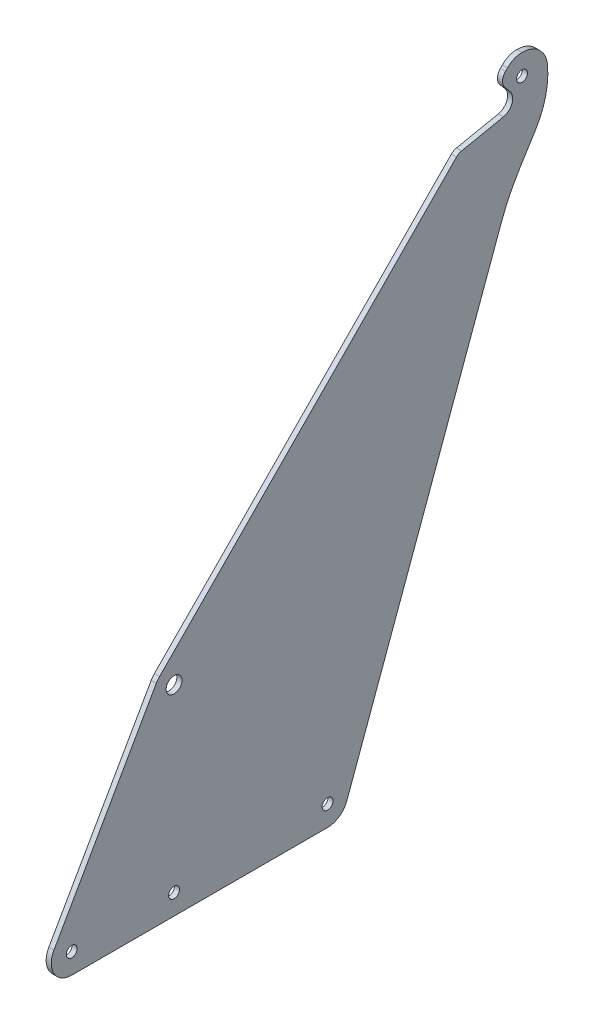
SolidWorks part; units mm, degrees
material "1060 Alloy"
ref_plane "Front Plane" through (0, 0, 0) normal (0, 0, 1) x (1, 0, 0)
ref_plane "Top Plane" through (0, 0, 0) normal (0, 1, 0) x (1, 0, 0)
ref_plane "Right Plane" through (0, 0, 0) normal (1, 0, 0) x (0, 0, -1)
sketch "Sketch5" plane through (0, 0, 0) normal (-1, 0, 0) x (0, 0, 1)
  line L0 (0, 0) -> (473.0768, -42.2261)
  line L1 (0, 0) -> (122.9281, 458.7738)
  line L2 (0, 0) -> (75.945, 21.568)
  line L4 (0, 0) -> (-8.1905, 78.5222)
  line L6 (-8.1905, 78.5222) -> (19.0819, 71.2146)
  line L7 (75.945, 21.568) -> (73.4348, -6.5547)
  line L8 (75.945, 21.568) -> (-215.9, 219.1278)
  line L9 (-215.9, 219.1278) -> (-8.1905, 78.5222)
  line L10 (0, 0) -> (745.3451, 0) construction
  point P2 (0, 0)
  dimension "D1" = 250.825
  dimension "D2" = 352.425
  dimension "D3" = 75
  dimension "D4" = 5.101
  dimension "D5" = 215.9
sketch "Sketch1" plane through (0, 0, 0) normal (1, 0, 0) x (0, 0, -1)
  line L0 (-74.539, -105.3537) -> (-11.039, 6.2793)
  line L2 (-63.5, -124.333) -> (95.25, -124.333)
  line L5 (107.181, -115.985) -> (227.831, 214.7758)
  line L6 (206.8534, 228.0412) -> (-9.0466, 8.9134)
  arc A0 (-9.0466, 8.9134) -> (-11.039, 6.2793) centre (0, 0) ccw
  arc A1 (95.25, -124.333) -> (107.181, -115.985) centre (95.25, -111.633) ccw
  arc A2 (-74.539, -105.3537) -> (-63.5, -124.333) centre (-63.5, -111.633) ccw
  arc A3 (227.831, 214.7758) -> (206.8534, 228.0412) centre (215.9, 219.1278) ccw
  dimension "D1" = 158.75
  dimension "D2" = 111.633
  dimension "D4" = 25.4
  dimension "D5" = 95.25
  dimension "D7" = 25.4
extrude "Boss-Extrude1" add sketch "Sketch1" along normal blind 3.175 contours A1 L5 A3 L6 A0 L0 A2 L2
sketch "Sketch2" plane through (3.175, 0, 0) normal (1, 0, 0) x (0, 0, -1)
  circle A0 centre (-63.5, -111.633) radius 3.3782
  circle A1 centre (0, -111.633) radius 3.3782
  circle A2 centre (95.25, -111.633) radius 3.3782
  arc A3 (-74.539, -105.3537) -> (-63.5, -124.333) centre (-63.5, -111.633) ccw construction
  arc A4 (95.25, -124.333) -> (107.181, -115.985) centre (95.25, -111.633) ccw construction
  circle A5 centre (215.9, 219.1278) radius 3.3782
  dimension "D2" = 0
  dimension "D3" = 0
  dimension "D4" = 63.5
  dimension "D5" = 6.7564
  dimension "D1" = 6.7564
extrude "Cut-Extrude1" cut sketch "Sketch2" against normal up to next
hole_wizard "3/8 Clearance Hole1" positions "Sketch3" profile "Sketch4" hole size "3/8" standard "ANSI Inch" end condition through all
sketch "Sketch3" plane through (3.175, 0, 0) normal (1, 0, 0) x (0, 0, -1)
  point P0 (0, 0)
sketch "Sketch4" plane through (3.175, 0, 0) normal (0, 1, 0) x (0, 0, -1)
  line L0 (0, 0) -> (0, 3.175)
  line L1 (0, 3.175) -> (4.9022, 3.175)
  line L2 (4.9022, 3.175) -> (4.9022, 0)
  line L5 (4.9022, 0) -> (0, 0)
  line L11 (0, -6.35) -> (0, 107.95) construction
  dimension "Thru Hole Dia." = 9.8044
  dimension "Thru Hole Depth" = 3.175
sketch "Sketch6" plane through (3.175, 0, 0) normal (1, 0, 0) x (0, 0, -1)
  line L0 (204.3797, 202.9854) -> (176.549, 197.2838)
  line L1 (176.549, 197.2838) -> (201.5749, 222.6838)
  line L2 (206.8534, 228.0412) -> (-9.0466, 8.9134) construction
  line L3 (208.4051, 214.5916) -> (201.5749, 222.6838)
  arc A0 (204.3797, 202.9854) -> (208.4051, 214.5916) centre (202.946, 209.9838) ccw
  circle A2 centre (215.9, 219.1278) radius 3.3782 construction
  point P7 (0, 0)
  point P8 (0, 0)
  point P9 (189.1214, 210.0442)
  point P10 (203.9772, 225.1221)
  point P14 (0, 0)
  point P16 (199.9624, 221.0472)
  dimension "D1" = 14.2875
  dimension "D4" = 12.7
  dimension "D3" = 12.954
  dimension "D5" = 12.7
  dimension "D2" = 9.144
extrude "Cut-Extrude2" cut sketch "Sketch6" against normal through all
sketch "Sketch7" plane through (0, 0, 0) normal (1, 0, 0) x (0, 0, -1)
  line L0 (207.6179, 159.3617) -> (224.1816, 185.8277)
  line L1 (107.181, -115.985) -> (227.831, 214.7758) construction
  line L9 (204.3797, 202.9854) -> (176.549, 197.2838)
  line L10 (176.549, 197.2838) -> (-9.0466, 8.9134)
  line L11 (-11.039, 6.2793) -> (-74.539, -105.3537)
  line L12 (-63.5, -124.333) -> (95.25, -124.333)
  line L13 (107.181, -115.985) -> (227.831, 214.7758)
  line L14 (206.8534, 228.0412) -> (201.5749, 222.6838)
  line L15 (201.5749, 222.6838) -> (208.4051, 214.5916)
  line L20 (207.6179, 159.3617) -> (227.831, 214.7758)
  arc A0 (224.1816, 185.8277) -> (231.7093, 217.396) centre (181.1196, 212.7778) ccw
  arc A1 (231.7093, 217.396) -> (215.9, 231.8278) centre (215.9, 215.9528) ccw
  arc A2 (227.831, 214.7758) -> (206.8534, 228.0412) centre (215.9, 219.1278) ccw construction
  arc A8 (-9.0466, 8.9134) -> (-11.039, 6.2793) centre (0, 0) ccw
  arc A9 (-74.539, -105.3537) -> (-63.5, -124.333) centre (-63.5, -111.633) ccw
  arc A10 (95.25, -124.333) -> (107.181, -115.985) centre (95.25, -111.633) ccw
  arc A11 (227.831, 214.7758) -> (206.8534, 228.0412) centre (215.9, 219.1278) ccw
  arc A12 (204.3797, 202.9854) -> (208.4051, 214.5916) centre (202.946, 209.9838) ccw
  arc A16 (227.831, 214.7758) -> (215.9, 231.8278) centre (215.9, 219.1278) ccw
  point P8 (200.6958, 140.3849)
  point P9 (0, 0)
  point P13 (239.0512, 212.6108)
  point P14 (227.5671, 224.1783)
  point P15 (232.4127, 189.8528)
  point P16 (232.4127, 224.1447)
  point P17 (216.4392, 231.8164)
  point P18 (227.0906, 181.8894)
  point P19 (214.5537, 231.7563)
  point P20 (0, 0)
  point P22 (231.2154, 220.1305)
  point P23 (181.2331, 220.1909)
  point P28 (0, 0)
  point P33 (181.0694, 213.3864)
  dimension "D2" = 15.875
  dimension "D3" = 50.8
  dimension "D1" = 12
  dimension "D5" = 6.35
  dimension "D4" = 0
extrude "Boss-Extrude2" add sketch "Sketch7" along normal up to surface (3.175 mm away) up to face at (3.175, 68.989, -106.1932)
fillet "Fillet1" radius 127 1 edges at (1.5875, 159.3617, -207.6179)
fillet "Fillet2" radius 6.35 2 edges at (1.5875, 197.2838, -176.549) (1.5875, 222.6838, -201.5749)
